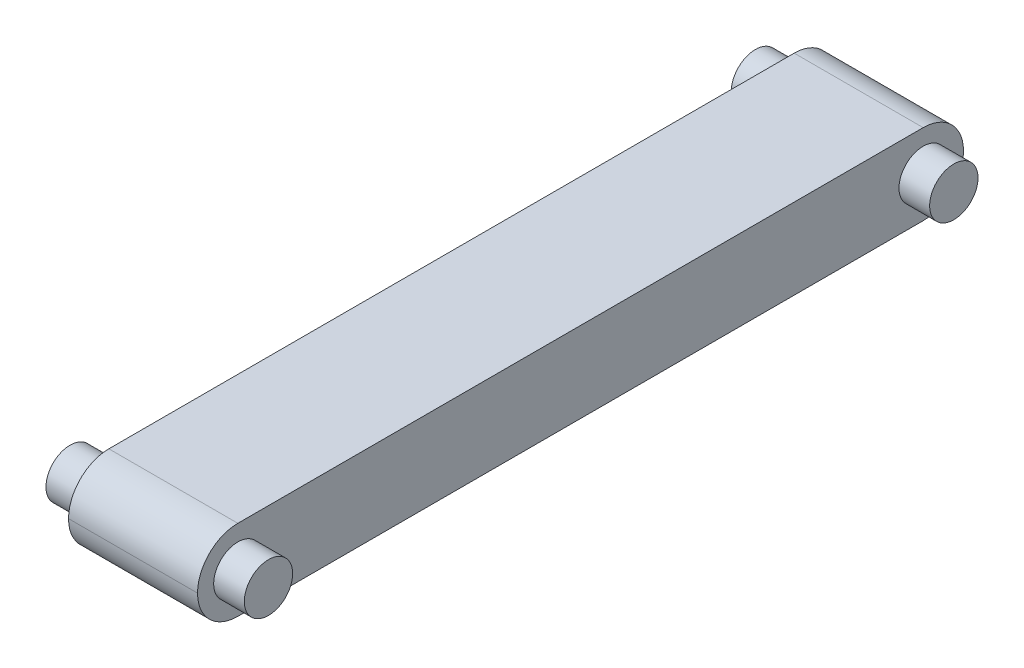
SolidWorks part; units mm, degrees
ref_plane "Front Plane" through (0, 0, 0) normal (0, 0, 1) x (1, 0, 0)
ref_plane "Top Plane" through (0, 0, 0) normal (0, 1, 0) x (1, 0, 0)
ref_plane "Right Plane" through (0, 0, 0) normal (1, 0, 0) x (0, 0, -1)
sketch "Sketch1" plane through (0, 0, 0) normal (0, 1, 0) x (1, 0, 0)
  line L1 (0, 0) -> (8, 0)
  line L2 (0, 0) -> (0, 47.5)
  line L3 (0, 47.5) -> (8, 47.5)
  line L4 (8, 0) -> (8, 47.5)
  dimension "D1" = 8
  dimension "D2" = 47.5
extrude "Boss-Extrude1" add sketch "Sketch1" along normal blind 5
sketch "Sketch2" plane through (8, 0, 0) normal (1, 0, 0) x (0, 0, -1)
  line L0 (0, 5) -> (47.5, 5) construction
  line L1 (0, 5) -> (0, 0) construction
  line L2 (0, 0) -> (47.5, 0) construction
  line L3 (47.5, 5) -> (47.5, 0) construction
  circle A0 centre (2.5, 2.5) radius 1.5
  circle A1 centre (45, 2.5) radius 1.5
  dimension "D1" = 2.5
  dimension "D2" = 2.5
  dimension "D3" = 2.5
  dimension "D4" = 2.5
  dimension "D5" = 3
  dimension "D6" = 3
extrude "Boss-Extrude2" add sketch "Sketch2" along normal blind 1.9 and the other way blind 10.4
fillet "Fillet1" radius 2.5 4 edges at (4, 0, -47.5) (4, 5, -47.5) (4, 0, 0) (4, 5, 0)
